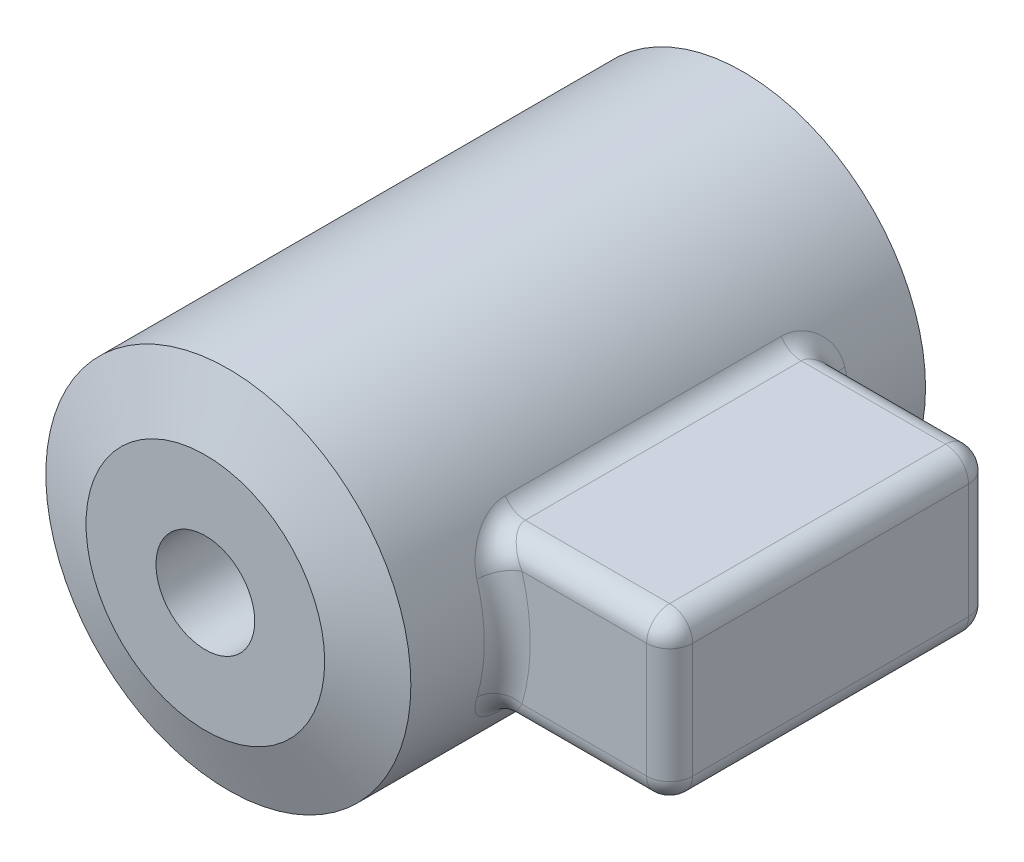
SolidWorks part; units mm, degrees
material "7075-T6 (SN)"
ref_plane "Front Plane" through (0, 0, 0) normal (0, 0, 1) x (1, 0, 0)
ref_plane "Top Plane" through (0, 0, 0) normal (0, 1, 0) x (1, 0, 0)
ref_plane "Right Plane" through (0, 0, 0) normal (1, 0, 0) x (0, 0, -1)
sketch "Sketch1" plane through (0, 0, 0) normal (0, 0, 1) x (1, 0, 0)
  circle A0 centre (0, 0) radius 7.9375
  dimension "D1" = 15.875
extrude "Boss-Extrude1" add sketch "Sketch1" along normal blind 24.384
sketch "Sketch2" plane through (0, 0, 24.384) normal (0, 0, 1) x (1, 0, 0)
  circle A0 centre (0, 0) radius 2.1463
  dimension "D1" = 4.2926
extrude "Cut-Extrude1" cut sketch "Sketch2" against normal through all
chamfer "Chamfer1" distance 1 angle 70 1 edges at (7.9375, 0, 24.384) first distance on face at (7.9375, 0, 24.384)
chamfer "Chamfer3" distance 1 angle 70 1 edges at (7.9375, 0, 0) first distance on face at (7.9375, 0, 23.384)
ref_plane "Plane2" through (5, 0, 0) normal (1, 0, 0) x (0, 0, -1)
sketch "Sketch3" plane through (5, 0, 0) normal (1, 0, 0) x (0, 0, -1)
  line L0 (8.7312, 0) -> (-8.7312, 0) construction
  line L1 (-19.192, 3.5) -> (-5.192, 3.5)
  line L2 (-19.192, 3.5) -> (-19.192, -3.5)
  line L3 (-19.192, -3.5) -> (-5.192, -3.5)
  line L4 (-5.192, 3.5) -> (-5.192, -3.5)
  line L5 (-19.192, 3.5) -> (-5.192, -3.5) construction
  line L6 (-19.192, -3.5) -> (-5.192, 3.5) construction
  line L7 (0, 8.7312) -> (0, -8.7312) construction
  point P0 (-12.192, 0)
  dimension "D1" = 12.192
  dimension "D2" = 7
  dimension "D3" = 14
extrude "Boss-Extrude2" add sketch "Sketch3" along normal blind 10
fillet "Fillet3" radius 1 12 edges at (7.9375, 0, 5.192) (11.0621, -3.5, 5.192) (7.1242, -3.5, 12.192) (7.1242, 3.5, 12.192) (11.0621, 3.5, 5.192) (11.0621, -3.5, 19.192) (7.9375, 0, 19.192) (11.0621, 3.5, 19.192) (15, -3.5, 12.192) (15, 0, 19.192) (15, 3.5, 12.192) (15, 0, 5.192)
equation "\"FrangiboltTotalDiameter\"= .625in"
equation "\"FrangiboltTotalLength\"= .960in"
equation "\"FrangiboltThruHoleDiameter\"= .169in"
equation "\"D1@Sketch1\"=\"FrangiboltTotalDiameter\""
equation "\"D1@Boss-Extrude1\"=\"FrangiboltTotalLength\""
equation "\"D1@Sketch2\"=\"FrangiboltThruHoleDiameter\""
equation "\"D1@Sketch3\"=\"FrangiboltTotalLength\"/2"
